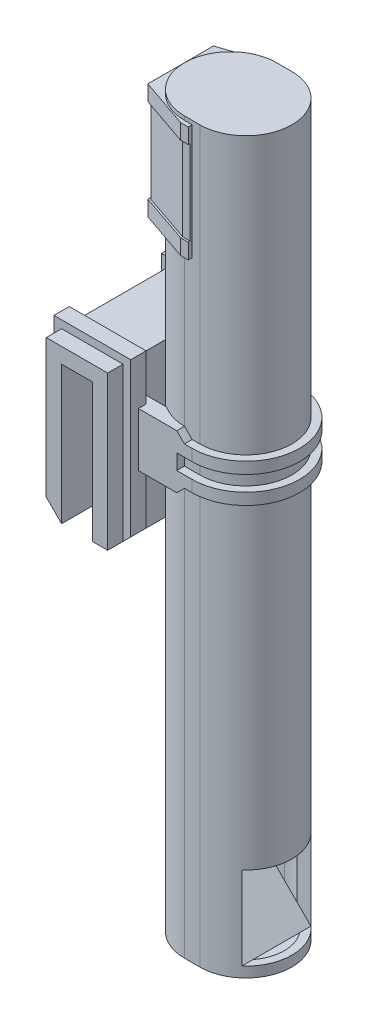
SolidWorks part; units mm, degrees
ref_plane "Front Plane" through (0, 0, 0) normal (0, 0, 1) x (1, 0, 0)
ref_plane "Top Plane" through (0, 0, 0) normal (0, 1, 0) x (1, 0, 0)
ref_plane "Right Plane" through (0, 0, 0) normal (1, 0, 0) x (0, 0, -1)
sketch "Sketch1" plane through (0, 0, 0) normal (0, 0, 1) x (1, 0, 0)
  line L0 (-51.9447, -77.5874) -> (-61.9447, -67.5874)
  line L1 (-51.9447, 12.4126) -> (-31.9447, 12.4126)
  line L2 (-51.9447, 12.4126) -> (-51.9447, -77.5874)
  line L4 (-31.9447, 12.4126) -> (-31.9447, -77.5874)
  line L5 (-61.9447, -67.5874) -> (-61.9447, 22.4126)
  line L6 (-61.9447, 22.4126) -> (-21.9447, 22.4126)
  line L7 (-21.9447, 22.4126) -> (-21.9447, -77.5874)
  line L8 (-21.9447, -77.5874) -> (-31.9447, -77.5874)
  line L9 (-21.9447, 9.0563) -> (-31.9447, 9.0563) construction
  line L10 (-42.9825, 22.4126) -> (-42.9825, 12.4126) construction
  line L11 (-61.9447, 9.0563) -> (-51.9447, 9.0563) construction
  dimension "D1" = 40
  dimension "D2" = 90
  dimension "D3" = 45
  dimension "D4" = 10
extrude "Boss-Extrude1" add sketch "Sketch1" along normal blind 100
sketch "Sketch3" plane through (0, 0, 100) normal (0, 0, 1) x (1, 0, 0)
  line L0 (-61.9447, -67.5874) -> (-66.9447, -67.5874)
  line L1 (-41.2735, 22.4126) -> (-41.2735, 27.4126)
  line L2 (-21.9447, 22.4126) -> (-61.9447, 22.4126) construction
  line L3 (-21.9447, -33.0039) -> (-16.9447, -33.0039)
  line L4 (-21.9447, -77.5874) -> (-21.9447, 22.4126) construction
  line L5 (-66.9447, -67.5874) -> (-66.9447, 27.4126)
  line L6 (-66.9447, 27.4126) -> (-16.9447, 27.4126)
  line L7 (-16.9447, 27.4126) -> (-16.9447, -72.5874)
  line L8 (-16.9447, -72.5874) -> (-21.9447, -77.5874)
  line L9 (-21.9447, -77.5874) -> (-21.9447, 22.4126)
  line L10 (-21.9447, 22.4126) -> (-61.9447, 22.4126)
  line L11 (-61.9447, 22.4126) -> (-61.9447, -67.5874)
  line M8 (-21.9447, -77.5874) -> (-21.9447, 22.4126)
  line M9 (-21.9447, 22.4126) -> (-61.9447, 22.4126)
  line M10 (-61.9447, 22.4126) -> (-61.9447, -67.5874)
  dimension "D1" = 5
extrude "Boss-Extrude2" add sketch "Sketch3" against normal blind 10 from offset 10 contours L6 L5 L0 L1 M10 M9 | L7 L6 L1 L3 M9 M8 | L8 L7 L3 M8 region at (-62.1509, -12.0456, 100) region at (-40.6222, 24.9126, 100) region at (-19.4942, -54.0704, 100) offset against normal yes
ref_plane "Plane1" through (0, 0, 50) normal (0, 0, -1) x (-1, 0, 0)
mirror "Mirror1" about plane through (0, 0, 50) normal (0, 0, -1) of "Boss-Extrude2"
sketch "Sketch4" plane through (-21.9447, 0, 0) normal (1, 0, 0) x (0, 0, -1)
  line L0 (-85, 30.3631) -> (-85, -69.6369) construction
  line L1 (-50, -22) -> (-50, 22) construction
  line L2 (-15, -37.5874) -> (-25, -37.5874)
  line L3 (-77.6412, -2.5874) -> (-77.6412, 22.4126) construction
  line L4 (-25, -2.5874) -> (-25, -37.5874)
  line L5 (-15, -72.5874) -> (-15, 27.4126) construction
  line L6 (-15, -2.5874) -> (-25, -2.5874)
  line L7 (-85, -2.5874) -> (-75, -2.5874)
  line L8 (-85, -2.5874) -> (-85, -37.5874)
  line L9 (-85, -37.5874) -> (-75, -37.5874)
  line L10 (-75, -2.5874) -> (-75, -37.5874)
  line L11 (-80, 22.4126) -> (-20, 22.4126) construction
  line L12 (-15, -2.5874) -> (-15, -37.5874)
  dimension "D1" = 25
  dimension "D2" = 35
  dimension "D3" = 10
  dimension "D4" = 25
extrude "Boss-Extrude3" add sketch "Sketch4" along normal blind 30
sketch "Sketch7" plane through (0, -2.5874, 0) normal (0, 1, 0) x (1, 0, 0)
  line L1 (8.0553, -15) -> (8.0553, -25) construction
  line L2 (8.0553, -75) -> (8.0553, -85) construction
  line L3 (8.0553, -20) -> (18.0553, -20)
  line L4 (8.0553, -80) -> (18.0553, -80)
  line L5 (-21.9447, -40.6008) -> (-21.9447, -59.3992)
  line L6 (-21.9447, -59.3992) -> (-20.4342, -59.3992)
  line L8 (-21.9447, -40.6008) -> (-20.4342, -40.6008)
  line L9 (-20.4342, -59.3992) -> (-20.4342, -40.6008)
  arc A0 (8.0553, -20) -> (8.0553, -80) centre (8.0553, -50) ccw
  arc A1 (18.0553, -80) -> (18.0553, -20) centre (18.0553, -50) ccw
  point P11 (-21.9447, -50)
  line M4 (8.0553, -85) -> (8.0553, -75)
  line M5 (8.0553, -75) -> (-21.9447, -75)
extrude "Boss-Extrude6" add sketch "Sketch7" along normal up to surface and the other way up to surface contours A0 L5 L6 | A0 L8 L5 | A0 L9 region at (-21.4936, -2.5874, 42.9386) region at (-21.0397, -2.5874, 50) region at (-21.4936, -2.5874, 57.0614) up to face at (-41.9447, 22.4126, 50) other way up to face at (-24.4447, -77.5874, 50)
extrude "Boss-Extrude7" add sketch "Sketch7<3>" along normal blind 175 and the other way blind 300 contours L4 A1 L3 A0 L9 M5 M4 | A0 M5 M4 | A0 L9 region at (13.4384, -2.5874, 49.5465) region at (-21.0397, -2.5874, 50) region at (1.7612, -2.5874, 77.015)
sketch "Sketch7<3>" plane through (0, -2.5874, 0) normal (0, 1, 0) x (1, 0, 0) same geometry as "Sketch7"
sketch "Sketch8" plane through (0, -2.5874, 0) normal (0, 1, 0) x (1, 0, 0)
  line L0 (18.0553, -85) -> (18.0553, -15) construction
  line L1 (18.0553, -85) -> (8.0553, -85)
  line L2 (8.0553, -85) -> (8.0553, -80)
  line L3 (8.0553, -80) -> (18.0553, -80)
  line L4 (18.0553, -15) -> (8.0553, -15)
  line L5 (8.0553, -15) -> (8.0553, -20)
  line L6 (8.0553, -20) -> (18.0553, -20)
  arc A0 (18.0553, -85) -> (18.0553, -15) centre (18.0553, -50) ccw
  arc A1 (18.0553, -80) -> (18.0553, -20) centre (18.0553, -50) ccw
extrude "Boss-Extrude8" add sketch "Sketch8" against normal blind 25 from offset 5 offset against normal yes
chamfer "Chamfer2" distance 5 angle 45 4 edges at (8.0553, -7.5874, 17.5) (8.0553, -32.5874, 17.5) (8.0553, -32.5874, 82.5) (8.0553, -7.5874, 82.5)
extrude "Cut-Extrude1" cut sketch "Sketch8<2>" against normal mid plane 10 from offset 17.5 offset against normal yes
sketch "Sketch8<2>" plane through (0, -2.5874, 0) normal (0, 1, 0) x (1, 0, 0) same geometry as "Sketch8"
sketch "Sketch9" plane through (0, 172.4126, 0) normal (0, 1, 0) x (1, 0, 0)
  line L0 (8.0553, -20) -> (-21.9447, -30.3004)
  line L1 (-21.9447, -40.6008) -> (-21.9447, -20) construction
  line L2 (-21.9447, -30.3004) -> (-21.9447, -69.6996)
  line L3 (-21.9447, -80) -> (-21.9447, -59.3992) construction
  line L4 (-21.9447, -69.6996) -> (8.0553, -80)
  line L5 (8.0553, -80) -> (8.0553, -20)
  line L6 (8.0553, -50) -> (-21.9447, -50) construction
  line L7 (-21.9447, -40.6008) -> (-20.4342, -40.6008)
  line L8 (8.0553, -15) -> (8.0553, -20) construction
  line L9 (-21.9447, -59.3992) -> (-20.4342, -59.3992)
  line L10 (8.0553, -80) -> (8.0553, -85) construction
  line L11 (-21.9447, -69.6996) -> (-21.9447, -72.1996)
  line L12 (-21.9447, -30.3004) -> (-21.9447, -27.8004)
  line L14 (-24.4447, -28.6588) -> (-24.4447, -71.3412)
  line L15 (8.0553, -17.5) -> (-24.4447, -28.6588)
  line L16 (8.0553, -82.5) -> (-24.4447, -71.3412)
  line L17 (8.0553, -82.5) -> (13.0553, -82.5)
  line L18 (13.0553, -80) -> (13.0553, -85) construction
  line L19 (13.0553, -82.5) -> (13.0553, -80)
  line L20 (8.0553, -80) -> (18.0553, -80) construction
  line L21 (13.0553, -80) -> (8.0553, -80)
  line L22 (8.0553, -20) -> (13.0553, -20)
  line L23 (8.0553, -20) -> (18.0553, -20) construction
  line L24 (13.0553, -20) -> (13.0553, -17.5)
  line L25 (13.0553, -15) -> (13.0553, -20) construction
  line L26 (13.0553, -17.5) -> (8.0553, -17.5)
  arc A1 (-20.4342, -40.6008) -> (-20.4342, -59.3992) centre (8.0553, -50) ccw
  arc M12 (8.0553, -20) -> (8.0553, -80) centre (8.0553, -50) ccw
  line M13 (8.0553, -80) -> (18.0553, -80)
  line M15 (18.0553, -20) -> (8.0553, -20)
extrude "Boss-Extrude11" add sketch "Sketch9" against normal blind 75 from offset 2.5 contours L16 L11 L2 L12 L15 L14 | L7 L2 M12 | L2 L9 M12 | L24 L26 L15 L12 L0 M12 M15 | L17 L19 L4 L11 L16 M13 M12 | L4 M12 | L2 L7 L0 M12 | L9 L2 L4 M12 region at (-1.8078, 172.4126, 21.2734) region at (-18.6106, 172.4126, 32.8725) region at (-1.3705, 172.4126, 77.4529) region at (10.5553, 172.4126, 80.3727) region at (-23.1864, 172.4126, 50) region at (-21.4936, 172.4126, 42.9386) region at (-18.6106, 172.4126, 67.1275) region at (-21.4936, 172.4126, 57.0614) offset against normal yes
ref_plane "Plane2" through (0, 132.4126, 0) normal (0, 1, 0) x (1, 0, 0)
extrude "Cut-Extrude3" cut sketch "Sketch9<4>" against normal mid plane 55 from surface contours L24 L26 L15 L12 L0 M12 M15 | L16 L11 L2 L12 L15 L14 | L2 L7 L0 M12 | L2 L9 M12 | L7 L2 M12 | L9 L2 L4 M12 | L17 L19 L4 L11 L16 M13 M12 | L0 M12 | L4 M12 region at (-1.8078, 172.4126, 21.2734) region at (-1.3705, 172.4126, 22.5471) region at (-18.6106, 172.4126, 32.8725) region at (-1.3705, 172.4126, 77.4529) region at (10.5553, 172.4126, 80.3727) region at (-23.1864, 172.4126, 50) region at (-21.4936, 172.4126, 42.9386) region at (-18.6106, 172.4126, 67.1275) region at (-21.4936, 172.4126, 57.0614) starting at plane "Plane2"
sketch "Sketch9<4>" plane through (0, 172.4126, 0) normal (0, 1, 0) x (1, 0, 0) same geometry as "Sketch9"
sketch "Sketch10" plane through (0, 104.9126, 0) normal (0, 1, 0) x (1, 0, 0)
  line L0 (8.0553, -17.5) -> (8.0553, -20)
  line L1 (8.0553, -15) -> (8.0553, -20) construction
  line L2 (-24.4447, -33.0369) -> (-23.1947, -33.0369)
  line L3 (-24.4447, -28.6588) -> (-24.4447, -71.3412) construction
  line L4 (8.0553, -80) -> (8.0553, -82.5)
  line L5 (8.0553, -81.25) -> (13.0553, -81.25)
  line L6 (13.0553, -82.5) -> (13.0553, -80) construction
  line L7 (13.0553, -81.25) -> (13.0553, -18.75)
  line L8 (13.0553, -20) -> (13.0553, -17.5) construction
  line L9 (13.0553, -18.75) -> (8.0553, -18.75)
  line L10 (8.0553, -18.75) -> (-23.1947, -29.4796)
  line L11 (-23.1947, -29.4796) -> (-23.1947, -70.5204)
  line L12 (-23.1947, -70.5204) -> (8.0553, -81.25)
  line L13 (8.0553, -82.5) -> (-24.4447, -71.3412) construction
  line L14 (8.0553, -17.5) -> (-24.4447, -28.6588) construction
  line M5 (13.0553, -82.5) -> (13.0553, -80)
  line M6 (13.0553, -80) -> (8.0553, -80)
  line M7 (8.0553, -80) -> (-10.373, -73.6727)
  arc M8 (-10.373, -73.6727) -> (-10.373, -26.3273) centre (8.0553, -50) cw
  line M9 (-10.373, -26.3273) -> (8.0553, -20)
  line M10 (8.0553, -20) -> (13.0553, -20)
  line M11 (13.0553, -20) -> (13.0553, -17.5)
extrude "Boss-Extrude12" add sketch "Sketch10" along normal up to surface (55 mm away) contours L11 L12 L4 L0 L10 M7 M8 M9 | L7 M6 M10 M9 M8 M7 | L9 L0 M11 M10 | L4 L5 M5 M6 region at (10.5553, 104.9126, 19.375) region at (7.3566, 104.9126, 19.375) region at (-2.0268, 104.9126, 50) region at (10.5553, 104.9126, 80.625) up to face at (0.2696, 159.9126, 50)
sketch "Sketch11" plane through (0, 172.4126, 0) normal (0, 1, 0) x (1, 0, 0)
  line L0 (8.0553, -25) -> (18.0553, -25)
  line L1 (18.0553, -75) -> (8.0553, -75)
  line L2 (18.0553, -80) -> (18.0553, -20) construction
  line L4 (18.0553, -80) -> (13.0553, -80) construction
  line L6 (8.0553, -20) -> (18.0553, -20) construction
  line L7 (8.0553, -80) -> (8.0553, -20) construction
  line L8 (12.3298, -25) -> (12.3298, -20) construction
  arc A0 (18.0553, -75) -> (18.0553, -25) centre (18.0553, -50) ccw
  arc A1 (8.0553, -25) -> (8.0553, -75) centre (8.0553, -50) ccw
  arc A2 (18.0553, -80) -> (18.0553, -20) centre (18.0553, -50) ccw construction
  arc A3 (18.0553, -80) -> (18.0553, -20) centre (18.0553, -50) ccw construction
  point P15 (18.0553, -50)
extrude "Cut-Extrude4" cut sketch "Sketch11" against normal blind 465 from offset 5 contours A1 L1 A0 L0 offset against normal yes
sketch "Sketch13" plane through (-21.9447, 0, 0) normal (1, 0, 0) x (0, 0, -1)
  line L0 (-50, -302.5874) -> (-50, -234.9479)
  line L1 (-80, -302.5874) -> (-20, -302.5874) construction
  line L3 (-72.5, -241.6785) -> (-27.5, -241.6785)
  line L4 (-72.5, -241.6785) -> (-72.5, -295.8568)
  line L5 (-72.5, -295.8568) -> (-27.5, -295.8568)
  line L6 (-27.5, -241.6785) -> (-27.5, -295.8568)
  line L7 (-72.5, -241.6785) -> (-27.5, -295.8568) construction
  line L8 (-72.5, -295.8568) -> (-27.5, -241.6785) construction
  point P4 (-50, -268.7676)
extrude "Cut-Extrude6" cut sketch "Sketch13" against normal blind 39 from offset 80 contours L4 L5 L0 L3 | L6 L3 L0 L5 region at (-21.9447, -268.7676, 61.25) region at (-21.9447, -268.7676, 38.75)
sketch "Sketch15" plane through (0, 0, 27.5) normal (0, 0, 1) x (1, 0, 0)
  line L0 (37.8985, -295.8568) -> (-16.9447, -241.0137)
  line L1 (-16.9447, 167.4126) -> (-16.9447, -297.5874) construction
  line L2 (-16.9447, -241.0137) -> (-16.9447, -246.8949)
  line L3 (-16.9447, -246.8949) -> (32.0172, -295.8568)
  line L4 (28.9526, -295.8568) -> (37.8985, -295.8568) construction
  line L5 (32.0172, -295.8568) -> (37.8985, -295.8568)
extrude "Boss-Extrude13" add sketch "Sketch15" along normal up to surface (45 mm away) contours L0 L2 L3 L5 up to face at (33.4255, -268.7676, 72.5)
sketch "Sketch16" plane through (0, -302.5874, 0) normal (0, -1, 0) x (1, 0, 0)
  line L0 (-16.9447, 72.5) -> (-16.9447, 66.5831)
  line L1 (-16.9447, 72.5) -> (-11.7878, 72.5)
  line L2 (-16.9447, 72.5) -> (-11.7878, 72.5) construction
  line L3 (-16.9447, 27.5) -> (-16.9447, 33.4169)
  line L4 (-16.9447, 27.5) -> (-11.7878, 27.5)
  arc A0 (-11.7878, 72.5) -> (-16.9447, 66.5831) centre (8.0553, 50) ccw
  arc A1 (-16.9447, 33.4169) -> (-11.7878, 27.5) centre (8.0553, 50) ccw
extrude "Cut-Extrude7" cut sketch "Sketch16" against normal blind 72
scale "Scale1" scale about centroid uniform scaling yes scale factor 1.3
